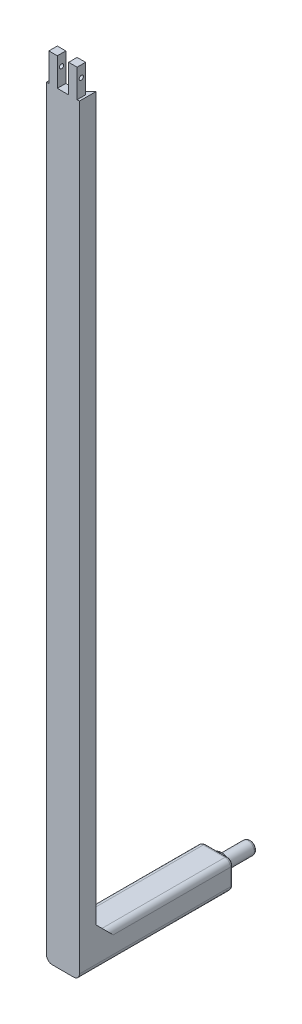
SolidWorks part; units mm, degrees
ref_plane "Front Plane" through (0, 0, 0) normal (0, 0, 1) x (1, 0, 0)
ref_plane "Top Plane" through (0, 0, 0) normal (0, 1, 0) x (1, 0, 0)
ref_plane "Right Plane" through (0, 0, 0) normal (1, 0, 0) x (0, 0, -1)
sketch "Sketch2" plane through (0, 0, 0) normal (0, 0, 1) x (1, 0, 0)
  line L1 (0, 0) -> (-6, 0)
  line L2 (0, 0) -> (0, -270)
  line L3 (0, -270) -> (-6, -270)
  line L4 (-6, 0) -> (-6, -270)
  dimension "D1" = 6
  dimension "D2" = 270
extrude "Boss-Extrude1" add sketch "Sketch2" along normal blind 3
sketch "Sketch4" plane through (0, -270, 0) normal (0, -1, 0) x (-1, 0, 0)
  line L0 (0, 0) -> (-2.8284, 2.8284)
  line L1 (-2.8284, 2.8284) -> (-2.8284, -3)
  line L2 (-2.8284, -3) -> (0, -3)
  line L3 (0, -3) -> (0, 0)
  line L4 (3, 0) -> (3, -3.7119) construction
  line L5 (6, 0) -> (0, 0) construction
  line L6 (8.8284, -3) -> (6, -3)
  line L7 (8.8284, 2.8284) -> (8.8284, -3)
  line L8 (6, 0) -> (8.8284, 2.8284)
  line L9 (6, -3) -> (6, 0)
  dimension "D1" = 135
  dimension "D2" = 4
extrude "Boss-Extrude2" add sketch "Sketch4" against normal up to vertex (270 mm away) up to point (0, 0, 0)
sketch "Sketch5" plane through (0, 0, 0) normal (0, 1, 0) x (1, 0, 0)
  line L0 (2.8284, -3) -> (-8.8284, -3) construction
  line L1 (-8, -3) -> (-5, -3)
  line L2 (-8, -3) -> (-8, 0)
  line L3 (-8, 0) -> (-5, 0)
  line L4 (-5, -3) -> (-5, 0)
  line L5 (-3, 0) -> (-3, -4.0355) construction
  line L6 (0, 0) -> (-6, 0) construction
  line L7 (2, 0) -> (-1, 0)
  line L8 (-1, -3) -> (-1, 0)
  line L9 (2, -3) -> (-1, -3)
  line L10 (2, -3) -> (2, 0)
  dimension "D1" = 3
  dimension "D2" = 2
  dimension "D3" = 0
extrude "Boss-Extrude3" add sketch "Sketch5" along normal blind 10
sketch "Sketch6" plane through (2, 0, 0) normal (1, 0, 0) x (0, 0, -1)
  line L0 (-3, 10) -> (-3, 0) construction
  line L1 (-3, 10) -> (0, 10) construction
  circle A0 centre (-1.5, 6) radius 0.75
  dimension "D1" = 1.5
  dimension "D2" = 1.5
  dimension "D3" = 4
extrude "Cut-Extrude1" cut sketch "Sketch6" against normal blind 40
sketch "Sketch7" plane through (0, 0, 0) normal (0, 0, -1) x (-1, 0, 0)
  line L0 (-2.8284, 0) -> (-2.8284, -270) construction
  line L1 (8.8284, -270) -> (-2.8284, -270)
  line L2 (8.8284, -270) -> (8.8284, -260)
  line L3 (8.8284, -260) -> (-2.8284, -260)
  line L4 (-2.8284, -270) -> (-2.8284, -260)
  dimension "D1" = 10
extrude "Boss-Extrude4" add sketch "Sketch7" along normal blind 51.58
sketch "Sketch8" plane through (0, 0, -51.58) normal (0, 0, -1) x (-1, 0, 0)
  line L0 (-2.8284, -270) -> (8.8284, -270) construction
  line L1 (-2.8284, -260) -> (-2.8284, -270) construction
  circle A0 centre (3, -265) radius 2.25
  point P4 (3, -270)
  point P7 (-2.8284, -265)
  dimension "D1" = 0
  dimension "D2" = 0
  dimension "D3" = 4.5
extrude "Boss-Extrude5" add sketch "Sketch8" along normal blind 12
sketch "Sketch9" plane through (-8.8284, 0, 0) normal (-1, 0, 0) x (0, 0, 1)
  line L0 (-7, -260) -> (0, -260)
  line L1 (-51.58, -260) -> (-2.8284, -260) construction
  line L2 (0, -260) -> (0, -253)
  line L3 (0, -253) -> (-7, -260)
  dimension "D1" = 7
  dimension "D2" = 7
extrude "Boss-Extrude6" add sketch "Sketch9" against normal up to vertex (11.6569 mm away) up to point (2.8284, -260, -2.8284)
sketch "Sketch10" plane through (0, 0, -51.58) normal (0, 0, -1) x (-1, 0, 0)
  circle A0 centre (3, -265) radius 3.5
  dimension "D1" = 7
extrude "Boss-Extrude7" add sketch "Sketch10" along normal blind 2
fillet "Fillet1" radius 2 4 edges at (2.8284, -270, -24.29) (-8.8284, -270, -24.29) (2.8284, -260, -29.29) (-8.8284, -260, -29.29)
fillet "Fillet2" radius 1 9 edges at (-8.2426, -269.4142, -51.58) (2.2426, -269.4142, -51.58) (2.2426, -260.5858, -51.58) (-8.2426, -260.5858, -51.58) (-6.5, -265, -53.58) (-3, -270, -51.58) (2.8284, -265, -51.58) (-3, -260, -51.58) (-8.8284, -265, -51.58)
fillet "Fillet3" radius 1 1 edges at (-5.25, -265, -63.58)
